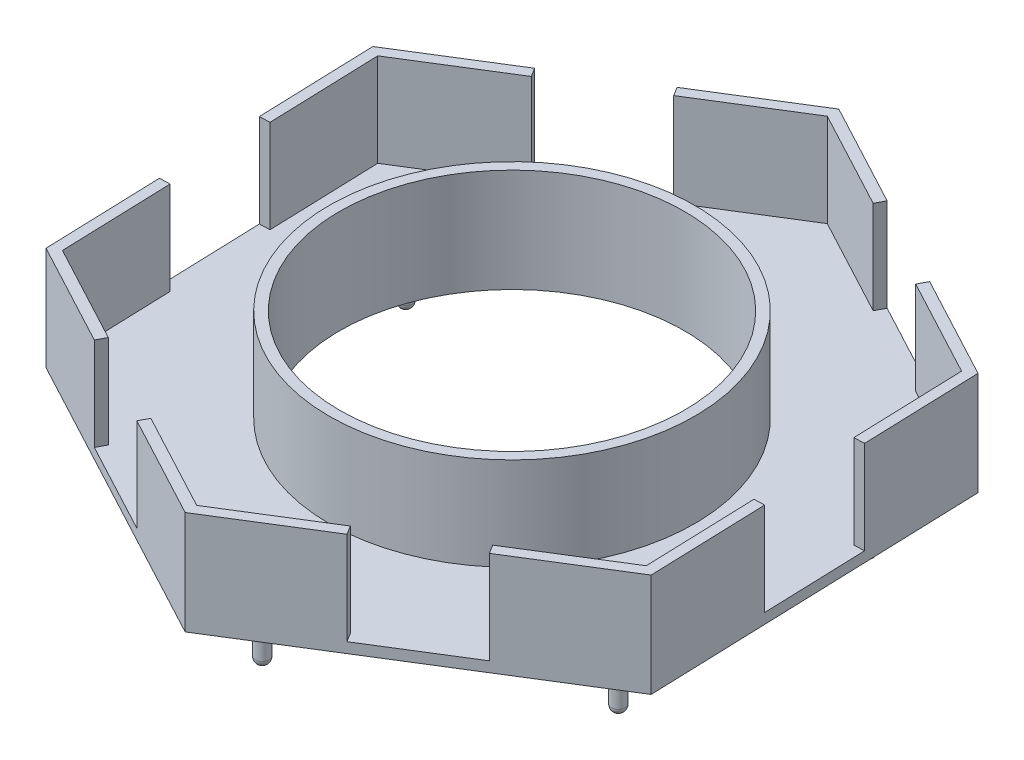
SolidWorks part; units mm, degrees
ref_plane "Front Plane" through (0, 0, 0) normal (0, 0, 1) x (1, 0, 0)
ref_plane "Top Plane" through (0, 0, 0) normal (0, 1, 0) x (1, 0, 0)
ref_plane "Right Plane" through (0, 0, 0) normal (1, 0, 0) x (0, 0, -1)
sketch "Sketch2" plane through (0, 0, 0) normal (0, 1, 0) x (1, 0, 0)
  line L1 (-83.3149, -51.8841) -> (3.2755, -98.0949)
  line L2 (3.2755, -98.0949) -> (86.5904, -46.2108)
  line L3 (86.5904, -46.2108) -> (83.3149, 51.8841)
  line L4 (83.3149, 51.8841) -> (-3.2755, 98.0949)
  line L5 (-3.2755, 98.0949) -> (-86.5904, 46.2108)
  line L6 (-86.5904, 46.2108) -> (-83.3149, -51.8841)
  circle A0 centre (0, 0) radius 50
  circle A1 centre (0, 0) radius 85 construction
extrude "Boss-Extrude1" add sketch "Sketch2" along normal blind 30
sketch "Sketch4" plane through (0, 0, 0) normal (0, -1, 0) x (1, 0, 0)
  circle A0 centre (-66.1672, -35.3115) radius 2
  circle A2 centre (0, 0) radius 50 construction
  circle A3 centre (-63.6642, 39.6467) radius 2
  circle A4 centre (2.503, 74.9582) radius 2
  circle A5 centre (66.1672, 35.3115) radius 2
  circle A6 centre (63.6642, -39.6467) radius 2
  circle A7 centre (-2.503, -74.9582) radius 2
  point P20 (0, 0)
  dimension "D1" = 75
  dimension "D2" = 6
extrude "Boss-Extrude2" add sketch "Sketch4" along normal blind 20 contours A3 | A0 | A5 | A4 | A7 | A6
fillet "Fillet1" radius 2 12 edges at (66.1672, 0, 37.3115) (66.1672, -20, 33.3115) (63.6642, 0, -37.6467) (63.6642, -20, -41.6467) (-2.503, 0, -72.9582) (-2.503, -20, -76.9582) (-66.1672, 0, -33.3115) (-66.1672, -20, -37.3115) (-63.6642, 0, 41.6467) (-63.6642, -20, 37.6467) (2.503, 0, 76.9582) (2.503, -20, 72.9582)
shell "Shell1" thickness 3 removed face at (0, 30, 0)
sketch "Sketch8" plane through (0, 30, 0) normal (0, 1, 0) x (1, 0, 0)
  line L0 (53.2531, 67.9272) -> (51.8407, 65.2805)
  line L1 (83.3149, 51.8841) -> (-3.2755, 98.0949) construction
  line L2 (80.3744, 50.0529) -> (-3.1599, 94.6327) construction
  line L3 (51.8407, 65.2805) -> (25.3738, 79.4051)
  line L4 (25.3738, 79.4051) -> (26.7862, 82.0518)
  line L5 (26.7862, 82.0518) -> (53.2531, 67.9272)
  line L6 (84.4521, 17.8283) -> (85.4532, -12.155)
  line L7 (82.4549, -12.2551) -> (81.4537, 17.7282)
  line L8 (85.4532, -12.155) -> (82.4549, -12.2551)
  line L9 (81.4537, 17.7282) -> (84.4521, 17.8283)
  line L10 (57.6658, -64.2235) -> (32.2001, -80.0822)
  line L11 (30.6142, -77.5356) -> (56.0799, -61.6769)
  line L12 (32.2001, -80.0822) -> (30.6142, -77.5356)
  line L13 (56.0799, -61.6769) -> (57.6658, -64.2235)
  line L14 (-26.7862, -82.0518) -> (-53.2531, -67.9272)
  line L15 (-51.8407, -65.2805) -> (-25.3738, -79.4051)
  line L16 (-53.2531, -67.9272) -> (-51.8407, -65.2805)
  line L17 (-25.3738, -79.4051) -> (-26.7862, -82.0518)
  line L18 (-84.4521, -17.8283) -> (-85.4532, 12.155)
  line L19 (-82.4549, 12.2551) -> (-81.4537, -17.7282)
  line L20 (-85.4532, 12.155) -> (-82.4549, 12.2551)
  line L21 (-81.4537, -17.7282) -> (-84.4521, -17.8283)
  line L22 (-57.6658, 64.2235) -> (-32.2001, 80.0822)
  line L23 (-30.6142, 77.5356) -> (-56.0799, 61.6769)
  line L24 (-32.2001, 80.0822) -> (-30.6142, 77.5356)
  line L25 (-56.0799, 61.6769) -> (-57.6658, 64.2235)
  point P9 (40.0197, 74.9895)
  point P32 (0, 0)
  dimension "D1" = 30
  dimension "D2" = 15
  dimension "D3" = 6
extrude "Cut-Extrude1" cut sketch "Sketch8" against normal blind 27
